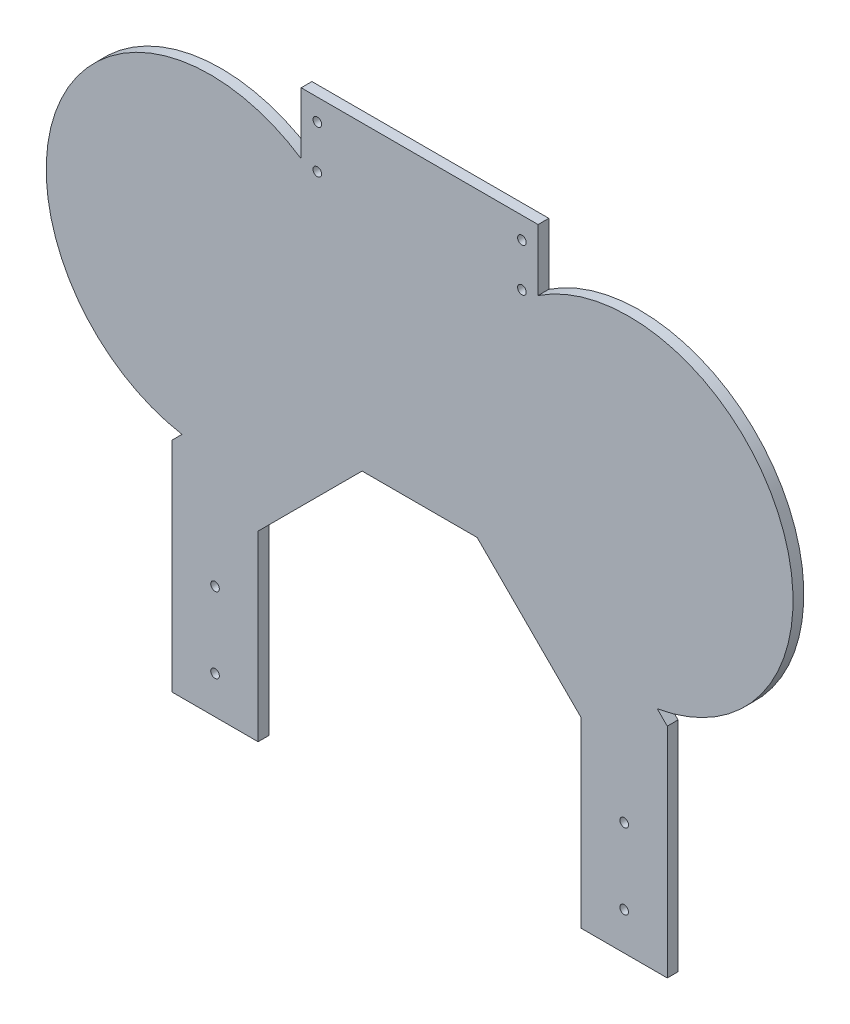
SolidWorks part; units mm, degrees
ref_plane "Front Plane" through (0, 0, 0) normal (0, 0, 1) x (1, 0, 0)
ref_plane "Top Plane" through (0, 0, 0) normal (0, 1, 0) x (1, 0, 0)
ref_plane "Right Plane" through (0, 0, 0) normal (1, 0, 0) x (0, 0, -1)
sketch "Sketch1" plane through (0, 0, 0) normal (0, 0, 1) x (1, 0, 0)
  line L1 (-100, -75) -> (100, -75)
  line L2 (-100, -75) -> (-100, 75)
  line L3 (-100, 75) -> (100, 75)
  line L4 (100, -75) -> (100, 75)
  line L5 (-100, -75) -> (100, 75) construction
  line L6 (-100, 75) -> (100, -75) construction
  line L8 (-47.5, 40) -> (47.5, 40) construction
  line L9 (0, 75) -> (0, -75) construction
  line L10 (-27, -44) -> (27, -44) construction
  line L11 (-27, -44) -> (-27, 28) construction
  line L12 (-27, 28) -> (27, 28) construction
  line L13 (27, -44) -> (27, 28) construction
  line L14 (-27, -44) -> (27, 28) construction
  line L15 (-27, 28) -> (27, -44) construction
  line L23 (-55, 70) -> (55, 70)
  line L24 (-55, 70) -> (-55, -70)
  line L25 (-55, -70) -> (55, -70)
  line L26 (55, 70) -> (55, -70)
  line L27 (-55, 70) -> (55, -70) construction
  line L28 (-55, -70) -> (55, 70) construction
  line L29 (-32.5, 70) -> (32.5, 70) construction
  line L30 (-32.5, 70) -> (-32.5, 55) construction
  line L31 (-32.5, 55) -> (32.5, 55) construction
  line L32 (32.5, 70) -> (32.5, 55) construction
  line L33 (-32.5, 70) -> (32.5, 55) construction
  line L34 (-32.5, 55) -> (32.5, 70) construction
  circle A2 centre (-47.5, 40) radius 2
  circle A3 centre (47.5, 40) radius 2
  circle A4 centre (-27, 28) radius 2 construction
  circle A5 centre (27, 28) radius 2 construction
  circle A6 centre (27, -44) radius 2 construction
  circle A7 centre (-27, -44) radius 2 construction
  circle A8 centre (-47.5, 60) radius 2
  circle A10 centre (47.5, 60) radius 2
  point P0 (0, 0)
  point P8 (0, 0)
  point P15 (0, 40)
  point P18 (0, -8)
  point P56 (0, 0)
  point P63 (0, 62.5)
  dimension "D3" = 4
  dimension "D4" = 20
  dimension "D5" = 4
  dimension "D8" = 4
  dimension "D1" = 150
  dimension "D2" = 200
  dimension "D6" = 72
  dimension "D7" = 54
  dimension "D14" = 30
  dimension "D15" = 140
  dimension "D16" = 110
  dimension "D17" = 95
  dimension "D18" = 12
  dimension "D19" = 15
  dimension "D20" = 65
extrude "Boss-Extrude1" add sketch "Sketch1" along normal blind 5 contours L23 L32 L31 L30 L24 L25 L26 A7 A6 A5 A4 A3 A2 region at (0, -0.1637, 0)
sketch "Sketch2" plane through (0, 0, 0) normal (0, 0, 1) x (1, 0, 0)
  line L0 (-55, -70) -> (-100.8579, -115.8579) construction
  line L1 (-55, 70) -> (-55, -70) construction
  line L2 (-55, -41.7157) -> (-115, -101.7157)
  line L3 (-26.7157, -70) -> (-86.7157, -130)
  line L4 (-55, -70) -> (55, -70) construction
  line L5 (-115, -101.7157) -> (-86.7157, -130)
  line L6 (-115, -101.7157) -> (-115, -203)
  line L7 (-75, -118.2843) -> (-75, -203)
  line L8 (-75, -203) -> (-115, -203)
  line L9 (0, 75) -> (0, -75) construction
  line L10 (-55, -41.7157) -> (-26.7157, -70)
  line L11 (-55, 70) -> (-55, -70) construction
  line L12 (-115, -203) -> (-75, -203) construction
  circle A0 centre (-95, -150.5) radius 2
  circle A1 centre (-95, -185.5) radius 2
  circle A2 centre (-95, -150.5) radius 2 construction
  circle A4 centre (-95, -185.5) radius 2 construction
  dimension "D1" = 135
  dimension "D2" = 40
  dimension "D3" = 40
  dimension "D4" = 75
  dimension "D5" = 0
extrude "Boss-Extrude2" add sketch "Sketch2" along normal blind 5 contours L8 L7 L3 L5 L6 | L10 L2 L5 L3 region at (-70.8579, -85.8579, 0) region at (-95.9289, -160.2024, 0)
mirror "Mirror1" about plane through (0, 0, 0) normal (1, 0, 0) of "Boss-Extrude2"
sketch "Sketch3" plane through (0, 0, 5) normal (0, 0, 1) x (1, 0, 0)
  line L0 (0, 31.3301) -> (0, 52.1198) construction
  circle A0 centre (-97.2, -22) radius 76.2
  circle A1 centre (-47.5, 40) radius 2 construction
  circle A2 centre (97.2, -22) radius 76.2
  point P3 (-91.0793, 11.0415)
  point P6 (-110.4, -20.143)
  point P7 (0, 0)
  dimension "D1" = 194.4
  dimension "D2" = 152.4
  dimension "D3" = 62
extrude "Boss-Extrude3" add sketch "Sketch3" against normal up to surface (5 mm away) up to face at (0, -95.388, 0)
